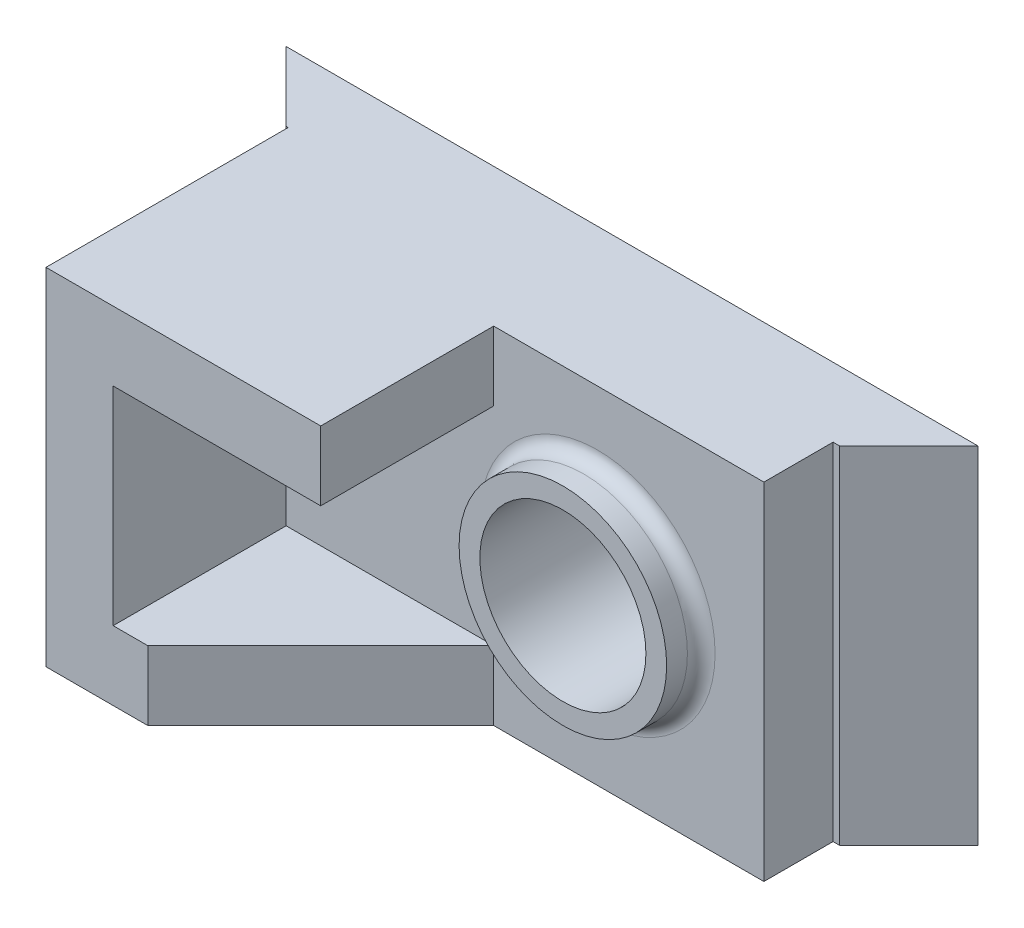
SolidWorks part; units mm, degrees
note: The reader was unsure of these and kept them because the rebuilt part matched: shared geometry of "Esquisse1<5>", "Esquisse1<6>", "Esquisse1<7>", "Esquisse1<8>".
ref_plane "Plan de face" through (0, 0, 0) normal (0, 0, 1) x (1, 0, 0)
ref_plane "Plan de dessus" through (0, 0, 0) normal (0, 1, 0) x (1, 0, 0)
ref_plane "Plan de droite" through (0, 0, 0) normal (1, 0, 0) x (0, 0, -1)
sketch "Esquisse1" plane through (0, 0, 0) normal (0, 0, 1) x (1, 0, 0)
  line L0 (-39.7066, 25) -> (-39.7066, -25)
  line L1 (-50, 25) -> (50, 25)
  line L2 (-50, 25) -> (-50, -25)
  line L3 (-50, -25) -> (50, -25)
  line L4 (50, 25) -> (50, -25)
  line L5 (-50, 25) -> (50, -25) construction
  line L6 (-50, -25) -> (50, 25) construction
  line L7 (-30, 25) -> (-30, -25)
  line L8 (-30, -15) -> (0, -15)
  line L9 (0, -15) -> (0, -25)
  line L10 (-30, 15) -> (0, 15)
  line L11 (0, 25) -> (0, 15)
  line L12 (39.0533, 25) -> (39.0533, -25)
  circle A0 centre (15, 0) radius 15
  circle A1 centre (15, 0) radius 12
  point P0 (0, 0)
  dimension "D6" = 30
  dimension "D7" = 24
  dimension "D1" = 50
  dimension "D2" = 100
  dimension "D3" = 30
  dimension "D4" = 30
  dimension "D5" = 10
  dimension "D8" = 25
  dimension "D9" = 35
extrude "Boss.-Extru.1" add sketch "Esquisse1" along normal blind 10 contours L2 L3 L0 L1
extrude "Boss.-Extru.2" add sketch "Esquisse1<5>" along normal blind 45 contours L7 L1 L0 L3 | L9 L8 L7 L3 | L11 L1 L7 L10
sketch "Esquisse1<5>" plane through (0, 0, 0) normal (0, 0, 1) x (1, 0, 0) same geometry as "Esquisse1"
extrude "Boss.-Extru.3" add sketch "Esquisse1<6>" along normal blind 10 contours L1 L12 L3 L4 | L2 L3 L0 L1
sketch "Esquisse1<6>" plane through (0, 0, 0) normal (0, 0, 1) x (1, 0, 0) same geometry as "Esquisse1"
extrude "Boss.-Extru.4" add sketch "Esquisse1<7>" along normal blind 25 separate body contours A0 A1 | A1
sketch "Esquisse1<7>" plane through (0, 0, 0) normal (0, 0, 1) x (1, 0, 0) same geometry as "Esquisse1"
extrude "Boss.-Extru.5" add sketch "Esquisse1<8>" along normal blind 20 contours L12 L1 L11 L10 L7 L8 L9 L3 A0
sketch "Esquisse1<8>" plane through (0, 0, 0) normal (0, 0, 1) x (1, 0, 0) same geometry as "Esquisse1"
fillet "Congé3" radius 2 1 edges at (30, 0, 20)
chamfer "Chanfrein2" distance 25 angle 45 1 edges at (0, -20, 45)
chamfer "Chanfrein21" distance 10 angle 45 1 edges at (50, 0, 10)
chamfer "Chanfrein22" distance 10 angle 45 1 edges at (-50, 0, 10)
